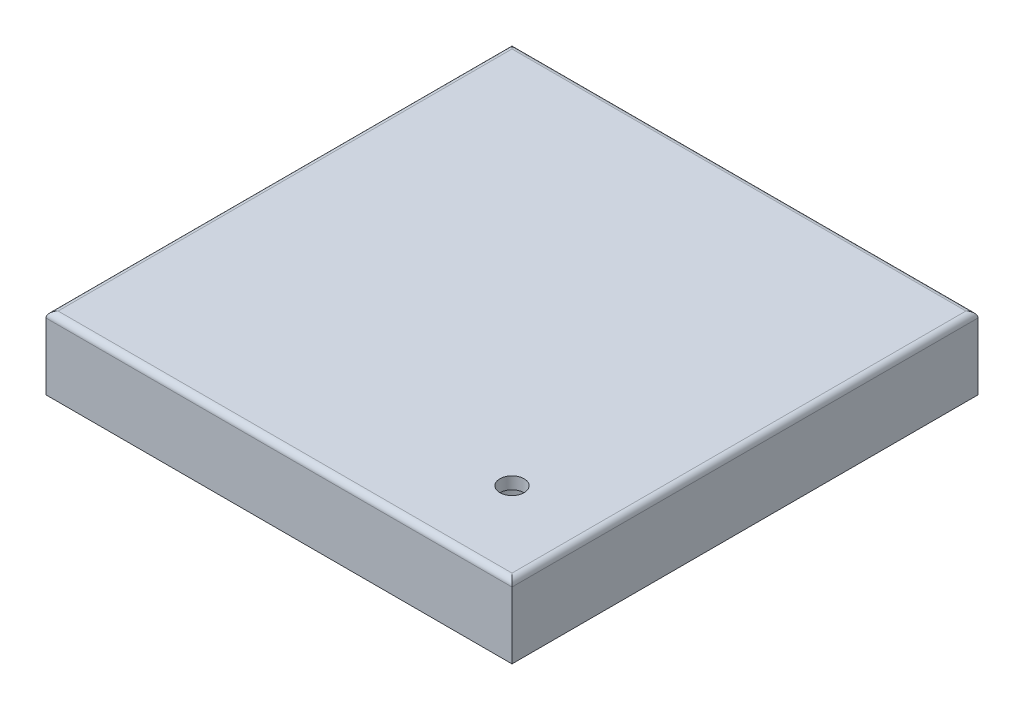
SolidWorks part; units mm, degrees
ref_plane "Front Plane" through (0, 0, 0) normal (0, 0, 1) x (1, 0, 0)
ref_plane "Top Plane" through (0, 0, 0) normal (0, 1, 0) x (1, 0, 0)
ref_plane "Right Plane" through (0, 0, 0) normal (1, 0, 0) x (0, 0, -1)
sketch "Sketch1" plane through (0, 0, 0) normal (0, 1, 0) x (1, 0, 0)
  line L0 (-47.5, 25.0543) -> (29.5, 25.0543) construction
  line L1 (29.5, 25.0543) -> (-9, 63.5543) construction
  line L2 (-9, -13.4457) -> (-9, -21.4272) construction
  line L3 (-47.5, 63.5543) -> (-47.5, -13.4457)
  line L4 (-47.5, 63.5543) -> (29.5, 63.5543)
  line L6 (-47.5, -13.4457) -> (29.5, -13.4457)
  line L7 (29.5, 63.5543) -> (29.5, -13.4457)
  line L13 (-46.2929, 62.3413) -> (-44.313, 60.3614) construction
  line L14 (-9, 63.5543) -> (-9, 25.0543) construction
  dimension "D1" = 77
  dimension "D2" = 38.5
extrude "Boss-Extrude1" add sketch "Sketch1" along normal blind 2
sketch "Sketch3" plane through (0, 0, 0) normal (0, -1, 0) x (1, 0, 0)
  line L0 (-47.5, -63.5543) -> (-47.5, 13.4457) construction
  line L1 (26, -60.0543) -> (-44, -60.0543)
  line L2 (26, -60.0543) -> (26, 9.9457)
  line L3 (26, 9.9457) -> (-44, 9.9457)
  line L4 (-44, -60.0543) -> (-44, 9.9457)
  line L5 (26, -60.0543) -> (-44, 9.9457) construction
  line L6 (26, 9.9457) -> (-44, -60.0543) construction
  line L7 (-47.5, 13.4457) -> (29.5, 13.4457) construction
  line L9 (24, -58.0543) -> (-42, -58.0543)
  line L10 (24, -58.0543) -> (24, 7.9457)
  line L11 (24, 7.9457) -> (-42, 7.9457)
  line L12 (-42, -58.0543) -> (-42, 7.9457)
  line L13 (24, -58.0543) -> (-42, 7.9457) construction
  line L14 (24, 7.9457) -> (-42, -58.0543) construction
  point P0 (-9, -25.0543)
  point P5 (-9, -25.0543)
  point P6 (-47.5, -25.0543)
  point P7 (-9, 13.4457)
  point P14 (-9, -25.0543)
  dimension "D1" = 70
  dimension "D2" = 70
  dimension "D3" = 2
extrude "Boss-Extrude2" add sketch "Sketch3" along normal blind 5 from offset 8
sketch "Sketch5" plane through (0, 0, 0) normal (0, -1, 0) x (1, 0, 0)
  line L1 (-47.5, 13.4457) -> (29.5, 13.4457)
  line L2 (-47.5, 13.4457) -> (-47.5, -63.5543)
  line L3 (-47.5, -63.5543) -> (29.5, -63.5543)
  line L4 (29.5, 13.4457) -> (29.5, -63.5543)
  line L5 (26, -60.0543) -> (-44, -60.0543)
  line L6 (26, -60.0543) -> (26, 9.9457)
  line L7 (26, 9.9457) -> (-44, 9.9457)
  line L8 (-44, -60.0543) -> (-44, 9.9457)
  point P12 (0, 0)
  point P13 (0, 0)
extrude "Boss-Extrude3" add sketch "Sketch5" along normal blind 10
sketch "Sketch7" plane through (0, 0, -63.5543) normal (0, 0, -1) x (-1, 0, 0)
  line L0 (44, -13) -> (-26, -13) construction
  line L1 (17, -13) -> (32, -13)
  line L2 (17, -13) -> (17, -10)
  line L3 (17, -10) -> (32, -10)
  line L4 (32, -13) -> (32, -10)
  line L5 (47.5, -10) -> (-29.5, -10) construction
  line L6 (44, -13) -> (44, -8) construction
  dimension "D1" = 15
  dimension "D2" = 12
extrude "Cut-Extrude2" cut sketch "Sketch7" against normal blind 10
chamfer "Chamfer1" distance 2 angle 45 4 edges at (-9, -8, 7.9457) (24, -8, -25.0543) (-9, -8, -58.0543) (-42, -8, -25.0543)
sketch "Sketch9" plane through (0, 0, 0) normal (0, -1, 0) x (1, 0, 0)
  line L0 (-42, 7.9457) -> (24, 7.9457) construction
  line L1 (24, 7.9457) -> (24, -58.0543) construction
  circle A0 centre (16, -0.0543) radius 6
  circle A1 centre (16, -0.0543) radius 8
  dimension "D1" = 12
  dimension "D2" = 2
extrude "Boss-Extrude6" add sketch "Sketch9" along normal blind 5
sketch "Sketch10" plane through (0, 0, 0) normal (0, -1, 0) x (1, 0, 0)
  circle A0 centre (16, -0.0543) radius 2
  dimension "D1" = 4
extrude "Cut-Extrude3" cut sketch "Sketch10" against normal blind 5
fillet "Fillet1" radius 1 4 edges at (-9, 2, -63.5543) (-47.5, 2, -25.0543) (-9, 2, 13.4457) (29.5, 2, -25.0543)
